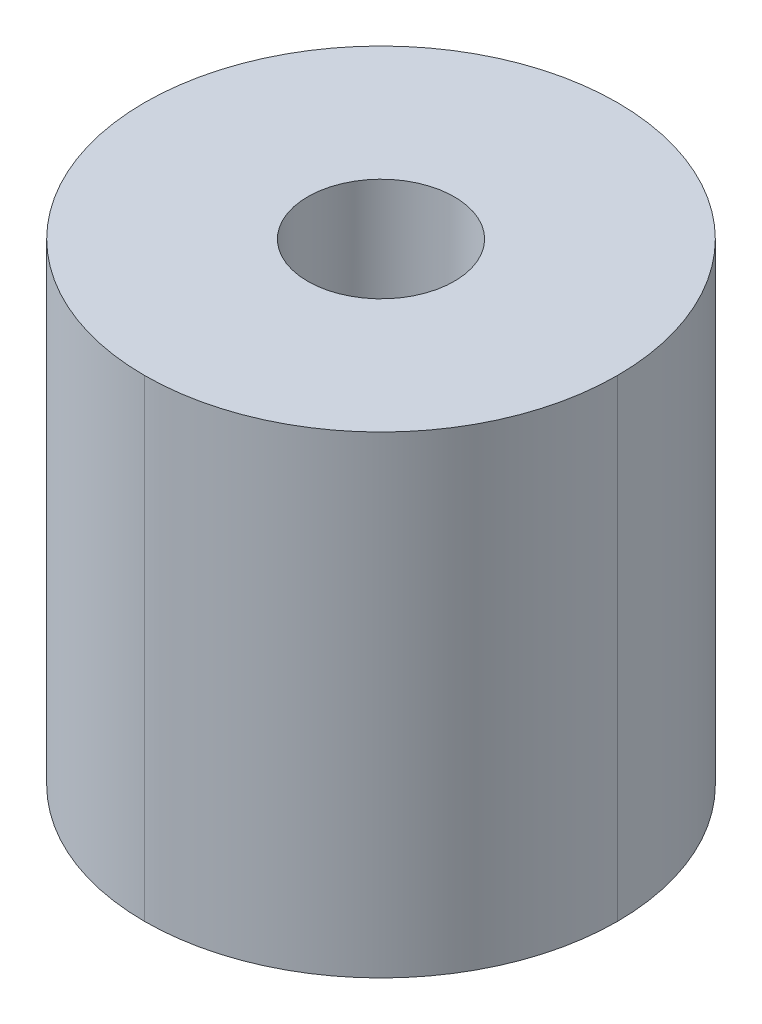
SolidWorks part; units mm, degrees
ref_plane "Front Plane" through (0, 0, 0) normal (0, 0, 1) x (1, 0, 0)
ref_plane "Top Plane" through (0, 0, 0) normal (0, 1, 0) x (1, 0, 0)
ref_plane "Right Plane" through (0, 0, 0) normal (1, 0, 0) x (0, 0, -1)
sketch "Sketch1" plane through (0, 0, 0) normal (0, 1, 0) x (1, 0, 0)
  line L1 (-10, -10) -> (10, -10)
  line L2 (-10, -10) -> (-10, 10)
  line L3 (-10, 10) -> (10, 10)
  line L4 (10, -10) -> (10, 10)
  line L5 (-10, -10) -> (10, 10) construction
  line L6 (-10, 10) -> (10, -10) construction
  point P0 (0, 0)
  dimension "D1" = 20
  dimension "D2" = 20
extrude "Boss-Extrude1" add sketch "Sketch1" along normal blind 20
sketch "Sketch2" plane through (0, 20, 0) normal (0, 1, 0) x (1, 0, 0)
  circle A0 centre (0, 0) radius 3.1
  dimension "D1" = 6.2
extrude "Cut-Extrude1" cut sketch "Sketch2" against normal blind 20
sketch "Sketch3" plane through (0, 0, 0) normal (0, -1, 0) x (1, 0, 0)
  circle A0 centre (0, 0) radius 5.075
  dimension "D1" = 10.15
extrude "Cut-Extrude2" cut sketch "Sketch3" against normal blind 9.3
chamfer "Chamfer1" distance 3 angle 45 1 edges at (0, 9.3, -3.1)
fillet "Fillet1" radius 10 4 edges at (10, 10, 10) (10, 10, -10) (-10, 10, -10) (-10, 10, 10)
